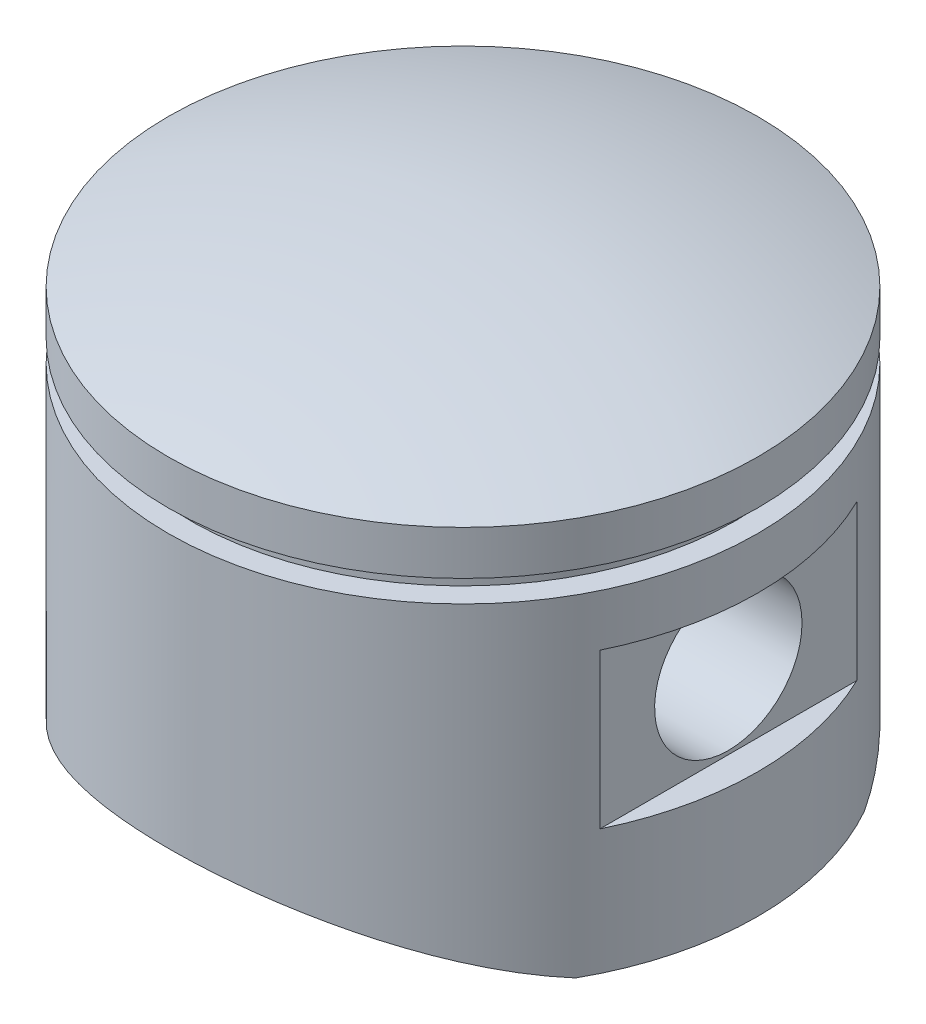
SolidWorks part; units mm, degrees
ref_plane "Front Plane" through (0, 0, 0) normal (0, 0, 1) x (1, 0, 0)
ref_plane "Top Plane" through (0, 0, 0) normal (0, 1, 0) x (1, 0, 0)
ref_plane "Right Plane" through (0, 0, 0) normal (1, 0, 0) x (0, 0, -1)
sketch "Sketch1" plane through (0, 0, 0) normal (0, 0, 1) x (1, 0, 0)
  line L0 (1016, 0) -> (1016, 1143)
  line L1 (1016, 1143) -> (939.8, 1143)
  line L2 (939.8, 1143) -> (939.8, 1219.2)
  line L3 (939.8, 1219.2) -> (1016, 1219.2)
  line L4 (1016, 1219.2) -> (1016, 1371.6)
  line L5 (1016, 1371.6) -> (0, 1371.6)
  line L6 (0, 1371.6) -> (0, 1193.8)
  line L7 (0, 1193.8) -> (838.2, 1193.8)
  line L8 (838.2, 1193.8) -> (838.2, 304.8)
  line L9 (838.2, 304.8) -> (939.8, 304.8)
  line L10 (939.8, 304.8) -> (939.8, 0)
  line L11 (939.8, 0) -> (1016, 0)
  line L12 (0, 0) -> (0, 797.0057) construction
  dimension "D1" = 76.2
  dimension "D2" = 304.8
  dimension "D3" = 0
  dimension "D4" = 177.8
  dimension "D5" = 76.2
  dimension "D6" = 1143
  dimension "D7" = 152.4
  dimension "D8" = 1016
  dimension "D9" = 76.2
  dimension "D10" = 76.2
  dimension "D11" = 177.8
revolve "Revolve1" add sketch "Sketch1" angle 360 about L12
sketch "Sketch2" plane through (0, 0, 0) normal (0, 0, 1) x (1, 0, 0)
  line L0 (-1016, 0) -> (1016, 0) construction
  line L1 (-914.4, 965.2) -> (-1139.7076, 965.2)
  line L2 (-914.4, 965.2) -> (-914.4, 431.8)
  line L3 (-914.4, 431.8) -> (-1139.7076, 431.8)
  line L4 (-1139.7076, 965.2) -> (-1139.7076, 431.8)
  line L5 (0, 0) -> (0, 1016.6393) construction
  line L6 (914.4, 431.8) -> (1139.7076, 431.8)
  line L7 (914.4, 965.2) -> (914.4, 431.8)
  line L8 (914.4, 965.2) -> (1139.7076, 965.2)
  line L9 (1139.7076, 965.2) -> (1139.7076, 431.8)
  dimension "D1" = 533.4
  dimension "D2" = 431.8
  dimension "D3" = 914.4
extrude "Cut-Extrude1" cut sketch "Sketch2" against normal through all both and the other way through all
sketch "Sketch3" plane through (0, 1193.8, 0) normal (0, -1, 0) x (1, 0, 0)
  line L0 (-711.2, 443.5919) -> (-711.2, -443.5919)
  line L1 (0, 0) -> (0, 606.3245) construction
  line L2 (711.2, 443.5919) -> (711.2, -443.5919)
  arc A0 (711.2, 443.5919) -> (711.2, -443.5919) centre (0, 0) cw
  circle A1 centre (0, 0) radius 838.2
  arc A2 (-711.2, 443.5919) -> (-711.2, -443.5919) centre (0, 0) ccw
  dimension "D2" = 711.2
  dimension "D1" = 0
extrude "Boss-Extrude1" add sketch "Sketch3" along normal up to surface (889 mm away) up to face at (939.8, 304.8, 0)
sketch "Sketch4" plane through (711.2, 0, 0) normal (-1, 0, 0) x (0, 0, 1)
  line L1 (317.5, 1193.8) -> (-317.5, 1193.8)
  line L2 (317.5, 1193.8) -> (317.5, 381)
  line L3 (317.5, 381) -> (-317.5, 381)
  line L4 (-317.5, 1193.8) -> (-317.5, 381)
  line L6 (443.5919, 1193.8) -> (-443.5919, 1193.8) construction
  dimension "D1" = 635
  dimension "D2" = 317.5
  dimension "D3" = 812.8
  dimension "D4" = 0
extrude "Boss-Extrude2" add sketch "Sketch4" along normal blind 254
fillet "Fillet1" radius 314.96 2 edges at (584.2, 381, 317.5) (584.2, 381, -317.5)
mirror "Mirror1" about plane through (0, 0, 0) normal (1, 0, 0) of "Fillet1", "Boss-Extrude2"
sketch "Sketch5" plane through (0, 0, 0) normal (1, 0, 0) x (0, 0, -1)
  line L1 (-1016, 0) -> (1016, 0) construction
  circle A0 centre (0, 698.5) radius 254
  dimension "D1" = 508
  dimension "D3" = 698.5
  dimension "D2" = 698.5
extrude "Cut-Extrude2" cut sketch "Sketch5" against normal through all both and the other way through all
sketch "Sketch6" plane through (0, 0, 0) normal (0, 0, 1) x (1, 0, 0)
  circle A0 centre (0, -1828.8) radius 2032
  dimension "D1" = 4064
  dimension "D3" = 0
  dimension "D2" = 1828.8
extrude "Cut-Extrude3" cut sketch "Sketch6" against normal through all both and the other way through all
dome "Dome1" faces to dome 1 distance 177.8 reverse direction no elliptical dome no face at (1016, 1371.6, 0) parameters "D1"=177.8
fillet "Fillet2" radius 25.4 10 edges at (457.2, 381, 0) (-457.2, 381, 0) (457.2, 944.88, -317.5) (457.2, 473.2496, -225.2504) (457.2, 473.2496, 225.2504) (457.2, 944.88, 317.5) (-457.2, 944.88, -317.5) (-457.2, 473.2496, -225.2504) (-457.2, 473.2496, 225.2504) (-457.2, 944.88, 317.5)
